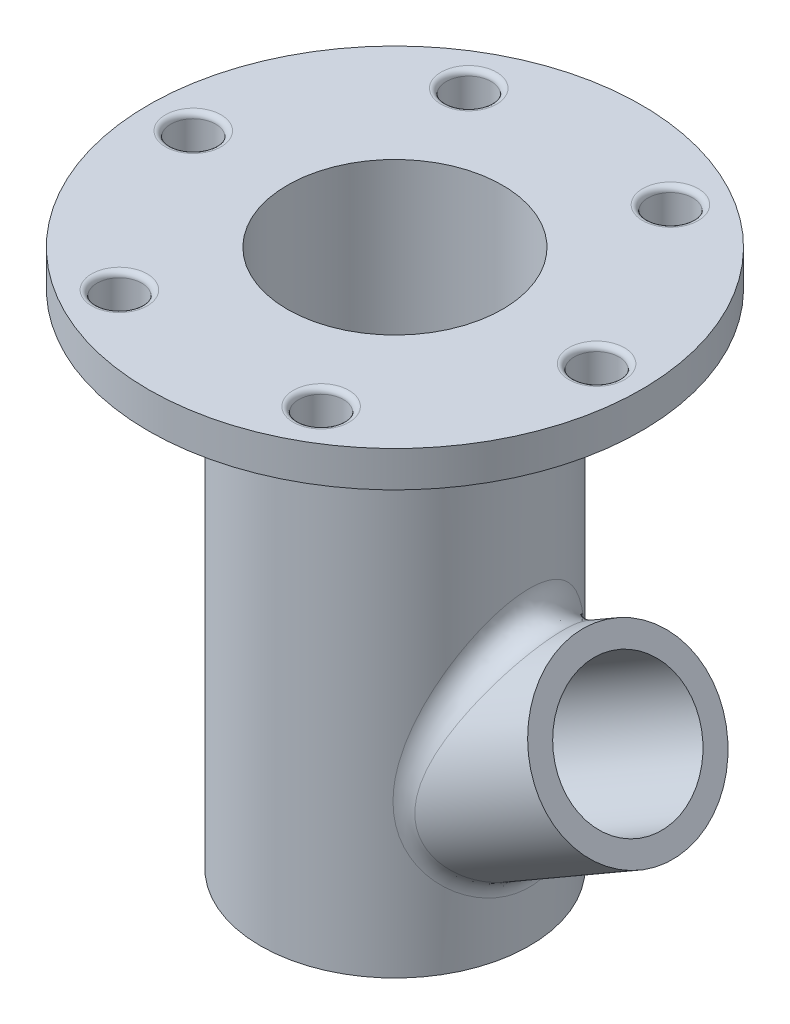
SolidWorks part; units mm, degrees
material "Plain Carbon Steel"
ref_plane "Front Plane" through (0, 0, 0) normal (0, 0, 1) x (1, 0, 0)
ref_plane "Top Plane" through (0, 0, 0) normal (0, 1, 0) x (1, 0, 0)
ref_plane "Right Plane" through (0, 0, 0) normal (1, 0, 0) x (0, 0, -1)
sketch "Sketch1" plane through (0, 0, 0) normal (0, 1, 0) x (1, 0, 0)
  circle A0 centre (0, 0) radius 19.05
  circle A1 centre (0, 0) radius 15.24
  dimension "D1" = 38.1
  dimension "D2" = 30.48
extrude "Boss-Extrude1" add sketch "Sketch1" along normal blind 71.12
sketch "Sketch2" plane through (0, 71.12, 0) normal (0, 1, 0) x (1, 0, 0)
  circle A0 centre (0, 0) radius 34.925
  circle A1 centre (0, 0) radius 15.24 construction
  circle A2 centre (0, 0) radius 15.24
  dimension "D1" = 69.85
extrude "Boss-Extrude2" add sketch "Sketch2" along normal blind 5.08
sketch "Sketch3" plane through (0, 76.2, 0) normal (0, 1, 0) x (1, 0, 0)
  circle A0 centre (0, 0) radius 28.575 construction
  circle A1 centre (28.575, 0) radius 3.175
  circle A2 centre (14.2875, -24.7467) radius 3.175
  circle A3 centre (-14.2875, -24.7467) radius 3.175
  circle A4 centre (-28.575, 0) radius 3.175
  circle A5 centre (-14.2875, 24.7467) radius 3.175
  circle A6 centre (14.2875, 24.7467) radius 3.175
  point P6 (-33.216, 0.0397)
  point P7 (-28.5124, -1.89)
  point P17 (0, 0)
  point P18 (-28.0258, -5.5755)
  point P19 (-28.5198, -1.7758)
  point P20 (0, 0)
  point P21 (-27.9832, -5.7854)
  point P22 (0, 0)
  point P23 (0, 0)
  dimension "D1" = 57.15
  dimension "D2" = 6.35
  dimension "D3" = 6
extrude "Cut-Extrude1" cut sketch "Sketch3" against normal up to next
sketch "Sketch4" plane through (0, 0, 0) normal (0, 0, 1) x (1, 0, 0)
  line L0 (0, 0) -> (0, 12.7) construction
  line L1 (0, 12.7) -> (32.9956, 31.75) construction
  dimension "D1" = 12.7
  dimension "D2" = 60
  dimension "D3" = 38.1
ref_plane "Plane1" through (32.9956, 31.75, 0) normal (0.866, 0.5, 0) x (0, 0, -1)
sketch "Sketch5" plane through (32.9956, 31.75, 0) normal (0.866, 0.5, 0) x (0, 0, -1)
  line L0 (0, -10.9985) -> (0, 0) construction
  circle A0 centre (0, 0) radius 12.7
  point P4 (0, 0)
  point P5 (0, 0)
  dimension "D1" = 25.4
extrude "Boss-Extrude3" add sketch "Sketch5" against normal up to next contours A0
sketch "Sketch6" plane through (38.4948, 22.225, 0) normal (0.866, 0.5, 0) x (0, 0, -1)
  line L0 (0, 0) -> (0, 10.9985) construction
  circle A0 centre (0, 10.9985) radius 9.525
  dimension "D1" = 19.05
extrude "Cut-Extrude2" cut sketch "Sketch6" against normal up to next
fillet "Fillet1" radius 0.762 6 edges at (14.2875, 76.2, 27.9217) (28.575, 76.2, 3.175) (14.2875, 76.2, -21.5717) (-14.2875, 76.2, -21.5717) (-28.575, 76.2, 3.175) (-14.2875, 76.2, 27.9217)
fillet "Fillet2" radius 3.175 2 edges at (0, 71.12, 19.05) (18.8817, 9.2297, -2.5263)
